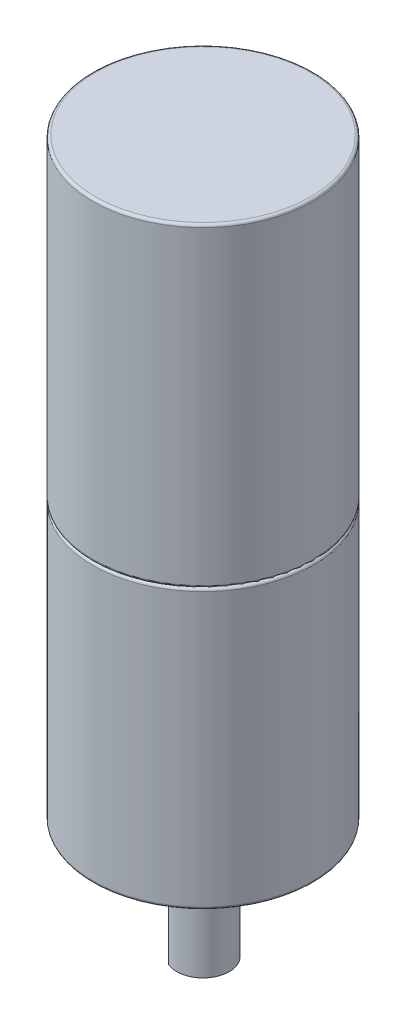
SolidWorks part; units mm, degrees
ref_plane "Alzado" through (0, 0, 0) normal (0, 0, 1) x (1, 0, 0)
ref_plane "Planta" through (0, 0, 0) normal (0, 1, 0) x (1, 0, 0)
ref_plane "Vista lateral" through (0, 0, 0) normal (1, 0, 0) x (0, 0, -1)
sketch "Croquis1" plane through (0, 0, 0) normal (0, 1, 0) x (1, 0, 0)
  circle A0 centre (0, 0) radius 21
  dimension "D1" = 42
extrude "Saliente-Extruir1" add sketch "Croquis1" along normal blind 60
fillet "Redondeo1" radius 0.5 2 edges at (0, 60, 21) (0, 0, 21)
sketch "Croquis2" plane through (0, 0, 0) normal (0, -1, 0) x (1, 0, 0)
  circle A0 centre (0, 0) radius 21
  dimension "D1" = 42
extrude "Saliente-Extruir2" add sketch "Croquis2" along normal blind 53
fillet "Redondeo2" radius 0.5 2 edges at (0, -53, -21) (0, 0, -21)
sketch "Croquis3" plane through (0, -53, 0) normal (0, -1, 0) x (1, 0, 0)
  line L0 (-11.5, 0) -> (0, 0) construction
  line L2 (11.5, -4.899) -> (11.5, 4.899)
  line L4 (-11.5, -4.899) -> (-11.5, 4.899)
  line L5 (0, 0) -> (11.5, 0) construction
  arc A0 (11.5, 4.899) -> (-11.5, 4.899) centre (0, 0) ccw
  arc A1 (-11.5, -4.899) -> (11.5, -4.899) centre (0, 0) ccw
  dimension "D1" = 25
  dimension "D2" = 9.798
  dimension "D3" = 9.798
extrude "Saliente-Extruir3" add sketch "Croquis3" along normal blind 2
sketch "Croquis4" plane through (0, -55, 0) normal (0, -1, 0) x (1, 0, 0)
  circle A0 centre (0, 0) radius 5
  dimension "D1" = 10
extrude "Saliente-Extruir4" add sketch "Croquis4" along normal blind 20.5
sketch "Croquis5" plane through (0, -75.5, 0) normal (0, -1, 0) x (1, 0, 0)
  line L0 (-2, 4.5826) -> (-2, -4.5826)
  line L1 (0, 0) -> (-2, 0) construction
  circle A0 centre (0, 0) radius 5 construction
  arc A2 (-2, 4.5826) -> (-2, -4.5826) centre (0, 0) ccw
  dimension "D1" = 2
extrude "Cortar-Extruir1" cut sketch "Croquis5" against normal blind 12
sketch "Croquis6" plane through (0, -53, 0) normal (0, -1, 0) x (1, 0, 0)
  circle A0 centre (0, 0) radius 17.5 construction
  circle A1 centre (-17.5, 0) radius 2
  circle A2 centre (0, 17.5) radius 2
  circle A3 centre (17.5, 0) radius 2
  circle A4 centre (0, -17.5) radius 2
  dimension "D1" = 35
  dimension "D2" = 4
  dimension "D3" = 4
  dimension "D4" = 4
  dimension "D5" = 4
extrude "Cortar-Extruir2" cut sketch "Croquis6" against normal blind 5
